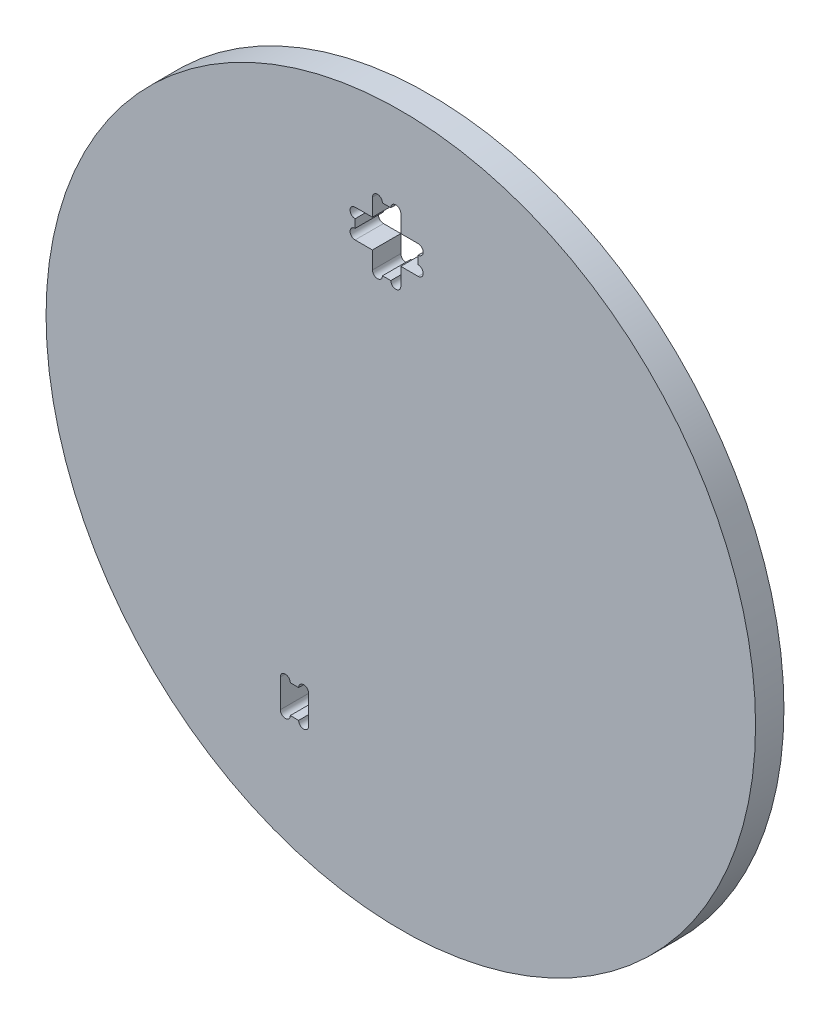
SolidWorks part; units mm, degrees
ref_plane "Piano frontale" through (0, 0, 0) normal (0, 0, 1) x (1, 0, 0)
ref_plane "Piano superiore" through (0, 0, 0) normal (0, 1, 0) x (1, 0, 0)
ref_plane "Piano destro" through (0, 0, 0) normal (1, 0, 0) x (0, 0, -1)
sketch "Schizzo1" plane through (0, 0, 0) normal (0, 0, 1) x (1, 0, 0)
  line L1 (-11.65, 168.4289) -> (-6.35, 168.4289)
  line L2 (-18, 168.4289) -> (-18, 157.4289)
  line L3 (-11.65, 128.4289) -> (-6.35, 128.4289)
  line L4 (0, 168.4289) -> (0, 157.4289)
  line L7 (-29, 157.4289) -> (-18, 157.4289)
  line L8 (-29, 151.0789) -> (-29, 145.7789)
  line L9 (-29, 139.4289) -> (-18, 139.4289)
  line L10 (11, 151.0789) -> (11, 145.7789)
  line L15 (0, 157.4289) -> (11, 157.4289)
  line L16 (-18, 139.4289) -> (-18, 128.4289)
  line L17 (0, 139.4289) -> (0, 128.4289)
  line L18 (0, 139.4289) -> (11, 139.4289)
  line L20 (-70.0973, -124.3311) -> (-64.7973, -124.3311)
  line L21 (-76.4473, -124.3311) -> (-76.4473, -142.3311)
  line L22 (-70.0973, -142.3311) -> (-64.7973, -142.3311)
  line L23 (-58.4473, -124.3311) -> (-58.4473, -142.3311)
  circle A0 centre (0, 0) radius 225
  arc A1 (0, 168.4289) -> (-6.35, 168.4289) centre (-3.175, 168.4289) ccw
  arc A2 (-18, 168.4289) -> (-11.65, 168.4289) centre (-14.825, 168.4289) cw
  arc A3 (0, 128.4289) -> (-6.35, 128.4289) centre (-3.175, 128.4289) cw
  arc A4 (-18, 128.4289) -> (-11.65, 128.4289) centre (-14.825, 128.4289) ccw
  arc A5 (11, 139.4289) -> (11, 145.7789) centre (11, 142.6039) ccw
  arc A6 (11, 157.4289) -> (11, 151.0789) centre (11, 154.2539) cw
  arc A7 (-29, 139.4289) -> (-29, 145.7789) centre (-29, 142.6039) cw
  arc A8 (-29, 157.4289) -> (-29, 151.0789) centre (-29, 154.2539) ccw
  arc A9 (-58.4473, -124.3311) -> (-64.7973, -124.3311) centre (-61.6223, -124.3311) ccw
  arc A10 (-76.4473, -124.3311) -> (-70.0973, -124.3311) centre (-73.2723, -124.3311) cw
  arc A11 (-58.4473, -142.3311) -> (-64.7973, -142.3311) centre (-61.6223, -142.3311) cw
  arc A12 (-76.4473, -142.3311) -> (-70.0973, -142.3311) centre (-73.2723, -142.3311) ccw
  point P3 (-9, 148.4289)
  point P8 (-9, 148.4289)
  dimension "D1" = 450
  dimension "D6" = 3.175
  dimension "D7" = 3.175
  dimension "D8" = 3.175
  dimension "D2" = 18
  dimension "D3" = 40
  dimension "D4" = 18
  dimension "D5" = 40
  dimension "D12" = 18
  dimension "D13" = 18
extrude "Estrusione-Estrusione1" add sketch "Schizzo1" along normal blind 18 contours A0
extrude "Taglio-Estrusione3" cut sketch "Schizzo1<7>" along normal blind 56 contours L7 L2 A2 L1 A1 L4 L15 A6 L10 A5 L18 L17 A3 L3 A4 L16 L9 A7 L8 A8
sketch "Schizzo1<7>" plane through (0, 0, 0) normal (0, 0, 1) x (1, 0, 0) same geometry as "Schizzo1"
extrude "Taglio-Estrusione4" cut sketch "Schizzo1<8>" along normal blind 110 contours L23 A11 L22 A12 L21 A10 L20 A9
sketch "Schizzo1<8>" plane through (0, 0, 0) normal (0, 0, 1) x (1, 0, 0) same geometry as "Schizzo1"
